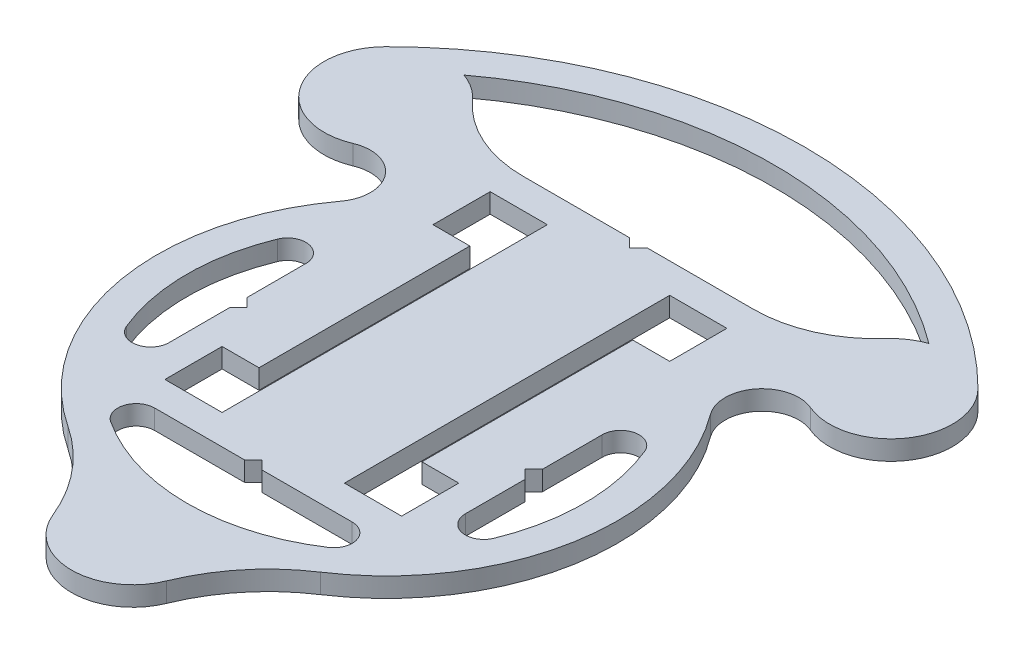
SolidWorks part; units mm, degrees
ref_plane "Front Plane" through (0, 0, 0) normal (0, 0, 1) x (1, 0, 0)
ref_plane "Top Plane" through (0, 0, 0) normal (0, 1, 0) x (1, 0, 0)
ref_plane "Right Plane" through (0, 0, 0) normal (1, 0, 0) x (0, 0, -1)
ref_plane "Plane1" through (0, 0, 26.3) normal (0, 0, 1) x (1, 0, 0)
ref_plane "Plane2" through (0, 0, 9.8) normal (0, 0, 1) x (1, 0, 0)
ref_axis "Axis1" through (0, 3.3337, 9.8) along (0, -1, 0)
sketch "Sketch1" plane through (0, 0, 0) normal (0, 1, 0) x (1, 0, 0)
  line L1 (-19.1, -26.3) -> (19.1, -26.3) construction
  line L2 (-19.1, -26.3) -> (-19.1, 26.3) construction
  line L4 (19.1, -26.3) -> (19.1, 26.3) construction
  line L5 (-19.1, -26.3) -> (19.1, 26.3) construction
  line L6 (-19.1, 26.3) -> (19.1, -26.3) construction
  line L10 (0, -9.8) -> (41.1, 31.3) construction
  line L19 (-19.1, 26.3) -> (19.1, 26.3) construction
  line L21 (0, -9.8) -> (-41.1, 31.3) construction
  line L22 (-41.1, 31.3) -> (41.1, 31.3) construction
  line L24 (0, -9.8) -> (0, 31.3) construction
  line L28 (41.1, 31.3) -> (48.1711, 38.3711) construction
  line L30 (24.1, -31.3) -> (24.1, 31.3) construction
  line L31 (-24.1, 31.3) -> (24.1, 31.3) construction
  line L32 (-24.1, -31.3) -> (-24.1, 31.3) construction
  line L33 (-24.1, -31.3) -> (24.1, -31.3) construction
  line L34 (0, -9.8) -> (0, -50.9) construction
  line L35 (-18.7393, 31.3) -> (18.7393, 31.3)
  line L36 (-19.1, -26.3) -> (-24.1, -31.3) construction
  line L38 (-24.1, -31.3) -> (-27.6405, -34.8405) construction
  line L40 (19.1, -26.3) -> (24.1, -31.3) construction
  line L42 (24.1, -31.3) -> (27.6405, -34.8405) construction
  line L43 (-24.1, -20.9298) -> (-24.1208, 1.6824)
  line L44 (24.1, -20.9298) -> (24.1, 1.3298)
  line L45 (-33.6464, -26.3) -> (-33.6464, 37.9667) construction
  line L46 (-33.6464, -26.3) -> (-19.1, -26.3) construction
  line L47 (-24.1, -22.6935) -> (-24.1, 6.3801) construction
  line L48 (-16.0634, -31.3) -> (16.0634, -31.3)
  circle A0 centre (-41.1, 31.3) radius 10 construction
  circle A1 centre (41.1, 31.3) radius 10 construction
  arc A2 (-48.1711, 38.3711) -> (48.1711, 38.3711) centre (0, -9.8) cw
  arc A3 (-37.814, 40.7447) -> (37.814, 40.7447) centre (0, -9.8) cw
  circle A4 centre (0, -50.9) radius 10 construction
  arc A5 (24.1, -31.3) -> (-24.1, -31.3) centre (0, -9.8) cw construction
  arc A7 (-33.6464, 37.9667) -> (-18.7393, 31.3) centre (-18.7393, 51.3) ccw
  arc A8 (18.7393, 31.3) -> (33.6464, 37.9667) centre (18.7393, 51.3) ccw
  arc A13 (-37.814, 40.7447) -> (-33.6464, 37.9667) centre (-41.1, 31.3) cw
  arc A14 (37.814, 40.7447) -> (33.6464, 37.9667) centre (41.1, 31.3) ccw
  arc A15 (27.6405, -34.8405) -> (-27.6405, -34.8405) centre (0, -9.8) cw construction
  arc A16 (9.2621, -54.6701) -> (20.5326, -40.9358) centre (37.0484, -65.9803) cw
  arc A17 (-20.5326, -40.9358) -> (-9.2621, -54.6701) centre (-37.0484, -65.9803) cw
  arc A24 (9.2621, -54.6701) -> (-9.2621, -54.6701) centre (0, -50.9) cw
  arc A26 (-37.1966, 22.0933) -> (-30.0379, 12.9916) centre (-34.8546, 16.5693) cw
  arc A27 (-30.0379, 12.9916) -> (-20.5326, -40.9358) centre (0.2124, -9.4778) ccw
  arc A28 (37.1966, 22.0933) -> (30.0379, 12.9916) centre (34.8546, 16.5693) ccw
  arc A29 (30.0379, 12.9916) -> (20.5326, -40.9358) centre (-0.2124, -9.4778) cw
  arc A30 (-24.1, 11.7) -> (24.1, 11.7) centre (0, -9.8) ccw construction
  arc A31 (-29.8751, 2.4695) -> (-24.1208, 1.6824) centre (-27.1, 1.3298) cw
  arc A32 (-24.1, -20.9298) -> (-29.8751, -22.0695) centre (-27.1, -20.9298) cw
  arc A33 (-17.7083, -36.8088) -> (-16.0634, -31.3) centre (-16.0634, -34.3) cw
  arc A34 (17.7083, -36.8088) -> (16.0634, -31.3) centre (16.0634, -34.3) ccw
  arc A35 (24.1, 1.3298) -> (29.8751, 2.4695) centre (27.1, 1.3298) cw
  arc A36 (29.8751, -22.0695) -> (24.1, -20.9298) centre (27.1, -20.9298) cw
  arc A37 (29.8751, 2.4695) -> (29.8751, -22.0695) centre (0, -9.8) cw
  arc A38 (-29.8751, -22.0695) -> (-29.8751, 2.4695) centre (0, -9.8) cw
  arc A39 (-17.7083, -36.8088) -> (17.7083, -36.8088) centre (0, -9.8) ccw
  arc A40 (-37.1966, 22.0933) -> (-48.1711, 38.3711) centre (-41.1, 31.3) cw
  arc A41 (37.1966, 22.0933) -> (48.1711, 38.3711) centre (41.1, 31.3) ccw
  point P0 (0, 0)
  point P59 (-26.6935, 4.3021)
  dimension "D5" = 5
  dimension "D8" = 30
  dimension "D9" = 3
  dimension "D10" = 6
  dimension "D3" = 20
  dimension "D4" = 5
  dimension "D6" = 20
  dimension "D7" = 5
  dimension "D1" = 38.2
  dimension "D2" = 52.6
extrude "Boss-Extrude1" add sketch "Sketch1" along normal blind 3.175
sketch "Sketch2" plane through (0, 3.175, 0) normal (0, 1, 0) x (1, 0, 0)
  line L0 (-10.1, 0) -> (10.1, 0) construction
  line L5 (-10.1, 26.3) -> (-10.1, -26.3) construction
  line L6 (10.1, 26.3) -> (10.1, -26.3) construction
  line L7 (-13.1, 17.3) -> (-13.1, -17.3) construction
  line L8 (13.1, 17.3) -> (13.1, -17.3) construction
  line L9 (-13.1, 0) -> (-10.1, 0) construction
  line L10 (10.1, 0) -> (13.1, 0) construction
  line L11 (-10.1, 26.3) -> (-19.1, 26.3) construction
  line L12 (-19.1, 26.3) -> (-19.1, 17.3) construction
  line L13 (-19.1, 17.3) -> (-13.1, 17.3) construction
  line L14 (-10.1, -26.3) -> (-19.1, -26.3) construction
  line L15 (-19.1, -26.3) -> (-19.1, -17.3) construction
  line L16 (-19.1, -17.3) -> (-13.1, -17.3) construction
  line L17 (10.1, 26.3) -> (19.1, 26.3) construction
  line L18 (19.1, 26.3) -> (19.1, 17.3) construction
  line L19 (19.1, 17.3) -> (13.1, 17.3) construction
  line L20 (10.1, -26.3) -> (19.1, -26.3) construction
  line L21 (19.1, -26.3) -> (19.1, -17.3) construction
  line L22 (19.1, -17.3) -> (13.1, -17.3) construction
  line L23 (-19.25, -17.15) -> (-13.25, -17.15)
  line L24 (-13.25, 17.15) -> (-13.25, -17.15)
  line L25 (-19.25, 17.15) -> (-13.25, 17.15)
  line L26 (-19.25, 26.45) -> (-19.25, 17.15)
  line L27 (-9.95, 26.45) -> (-19.25, 26.45)
  line L28 (-9.95, 26.45) -> (-9.95, -26.45)
  line L29 (-9.95, -26.45) -> (-19.25, -26.45)
  line L30 (-19.25, -26.45) -> (-19.25, -17.15)
  line L31 (19.25, -17.15) -> (13.25, -17.15)
  line L32 (13.25, 17.15) -> (13.25, -17.15)
  line L33 (19.25, 17.15) -> (13.25, 17.15)
  line L34 (19.25, 26.45) -> (19.25, 17.15)
  line L35 (9.95, 26.45) -> (19.25, 26.45)
  line L36 (9.95, 26.45) -> (9.95, -26.45)
  line L37 (9.95, -26.45) -> (19.25, -26.45)
  line L38 (19.25, -26.45) -> (19.25, -17.15)
  point P3 (0, 0)
  point P9 (-10.1, 0)
  point P12 (10.1, 0)
  point P15 (-13.1, 0)
  point P18 (13.1, 0)
  dimension "D1" = 20.2
  dimension "D2" = 52.6
  dimension "D3" = 3
  dimension "D4" = 34.6
  dimension "D5" = 9
  dimension "D6" = 0.15
  dimension "D7" = 0.15
extrude "Cut-Extrude3" cut sketch "Sketch2" against normal up to next
sketch "Sketch8" plane through (0, 3.175, 0) normal (0, 1, 0) x (1, 0, 0)
  line L0 (0, -9.8) -> (0, -31.3) construction
  line L1 (16.0634, -31.3) -> (-16.0634, -31.3) construction
  line L2 (0, -9.8) -> (-24.1104, -9.6237) construction
  line L3 (-24.1, -20.9298) -> (-24.1208, 1.6824) construction
  line L4 (0, -9.8) -> (24.1, -9.8) construction
  line L5 (24.1, 1.3298) -> (24.1, -20.9298) construction
  line L6 (0, -9.8) -> (0, 31.3) construction
  line L7 (-18.7393, 31.3) -> (18.7393, 31.3) construction
  line L8 (-22.702, -9.634) -> (-24.1117, -8.2152)
  line L9 (-24.1117, -8.2152) -> (-24.1091, -11.0321)
  line L10 (-24.1091, -11.0321) -> (-22.702, -9.634)
  line L11 (22.6858, -9.8) -> (24.1, -11.2142)
  line L12 (24.1, -11.2142) -> (24.1, -8.3858)
  line L13 (24.1, -8.3858) -> (22.6858, -9.8)
  line L14 (0, -29.8858) -> (-1.4142, -31.3)
  line L15 (-1.4142, -31.3) -> (1.4142, -31.3)
  line L16 (1.4142, -31.3) -> (0, -29.8858)
  line L17 (0, 29.8858) -> (-1.4142, 31.3)
  line L18 (-1.4142, 31.3) -> (1.4142, 31.3)
  line L19 (1.4142, 31.3) -> (0, 29.8858)
  point P16 (-24.1104, -9.6237)
  point P20 (24.1, -9.8)
  point P24 (0, -31.3)
  point P28 (0, 31.3)
  dimension "D1" = 2
extrude "Cut-Extrude4" cut sketch "Sketch8" against normal up to next
sketch "Sketch9" plane through (0, 3.175, 0) normal (0, 1, 0) x (1, 0, 0)
  line L1 (-48.1711, 38.3711) -> (-44.6355, 34.8355)
  line L2 (-34.0621, 49.1973) -> (-31.5621, 44.8671)
  line L3 (-17.6318, 56.0029) -> (-16.3377, 51.1733)
  line L4 (0, 58.3242) -> (0, 53.3242)
  line L5 (17.6318, 56.0029) -> (16.3377, 51.1733)
  line L6 (34.0621, 49.1973) -> (31.5621, 44.8671)
  line L7 (48.1711, 38.3711) -> (44.6355, 34.8355)
  line L8 (-48.1711, 38.3711) -> (-46.4033, 36.6033)
  line L9 (-43.7894, 42.3861) -> (-42.1824, 40.471)
  line L10 (-39.0744, 46.0041) -> (-37.6405, 43.9562)
  line L11 (-34.0621, 49.1973) -> (-32.8121, 47.0322)
  line L12 (-28.7905, 51.9415) -> (-27.734, 49.6757)
  line L13 (-23.2998, 54.2158) -> (-22.4448, 51.8666)
  line L14 (-17.6318, 56.0029) -> (-16.9848, 53.5881)
  line L15 (-11.8296, 57.2892) -> (-11.3955, 54.8272)
  line L16 (-5.9374, 58.0649) -> (-5.7195, 55.5745)
  line L17 (0, 58.3242) -> (0, 55.8242)
  line L18 (5.9374, 58.0649) -> (5.7195, 55.5745)
  line L19 (11.8296, 57.2892) -> (11.3955, 54.8272)
  line L20 (17.6318, 56.0029) -> (16.9848, 53.5881)
  line L21 (23.2998, 54.2158) -> (22.4448, 51.8666)
  line L22 (28.7905, 51.9415) -> (27.734, 49.6757)
  line L23 (34.0621, 49.1973) -> (32.8121, 47.0322)
  line L24 (39.0744, 46.0041) -> (37.6405, 43.9562)
  line L25 (43.7894, 42.3861) -> (42.1824, 40.471)
  line L26 (48.1711, 38.3711) -> (46.4033, 36.6033)
  line L27 (-48.1711, 38.3711) -> (-47.2872, 37.4872)
  line L28 (-47.323, 39.2044) -> (-46.4547, 38.3053)
  line L29 (-46.4606, 40.0229) -> (-45.6081, 39.1087)
  line L30 (-45.584, 40.8261) -> (-44.7476, 39.8972)
  line L31 (-44.6935, 41.614) -> (-43.8734, 40.6706)
  line L32 (-43.7894, 42.3861) -> (-42.9859, 41.4286)
  line L33 (-42.8719, 43.1424) -> (-42.0853, 42.171)
  line L34 (-41.9414, 43.8826) -> (-41.1719, 42.8976)
  line L35 (-40.9982, 44.6064) -> (-40.2459, 43.6081)
  line L36 (-40.0424, 45.3136) -> (-39.3077, 44.3023)
  line L37 (-39.0744, 46.0041) -> (-38.3575, 44.9801)
  line L38 (-38.0946, 46.6775) -> (-37.3956, 45.6412)
  line L39 (-37.1031, 47.3337) -> (-36.4223, 46.2854)
  line L40 (-36.1003, 47.9726) -> (-35.4379, 46.9125)
  line L41 (-35.0865, 48.5938) -> (-34.4427, 47.5224)
  line L42 (-34.0621, 49.1973) -> (-33.4371, 48.1147)
  line L43 (-33.0273, 49.7827) -> (-32.4212, 48.6895)
  line L44 (-31.9824, 50.3501) -> (-31.3955, 49.2464)
  line L45 (-30.9277, 50.8991) -> (-30.3602, 49.7853)
  line L46 (-29.8637, 51.4296) -> (-29.3157, 50.3061)
  line L47 (-28.7905, 51.9415) -> (-28.2622, 50.8086)
  line L48 (-27.7086, 52.4345) -> (-27.2002, 51.2926)
  line L49 (-26.6182, 52.9086) -> (-26.1298, 51.758)
  line L50 (-25.5198, 53.3636) -> (-25.0515, 52.2047)
  line L51 (-24.4135, 53.7994) -> (-23.9656, 52.6324)
  line L52 (-23.2998, 54.2158) -> (-22.8723, 53.0412)
  line L53 (-22.1791, 54.6127) -> (-21.7721, 53.4308)
  line L54 (-21.0515, 54.9899) -> (-20.6653, 53.8011)
  line L55 (-19.9176, 55.3475) -> (-19.5521, 54.1521)
  line L56 (-18.7776, 55.6852) -> (-18.433, 54.4836)
  line L57 (-17.6318, 56.0029) -> (-17.3083, 54.7955)
  line L58 (-16.4807, 56.3006) -> (-16.1783, 55.0877)
  line L59 (-15.3246, 56.5782) -> (-15.0434, 55.3602)
  line L60 (-14.1638, 56.8355) -> (-13.9039, 55.6128)
  line L61 (-12.9987, 57.0725) -> (-12.7602, 55.8455)
  line L62 (-11.8296, 57.2892) -> (-11.6126, 56.0582)
  line L63 (-10.657, 57.4855) -> (-10.4614, 56.2508)
  line L64 (-9.4811, 57.6612) -> (-9.3071, 56.4234)
  line L65 (-8.3022, 57.8164) -> (-8.1499, 56.5757)
  line L66 (-7.1209, 57.951) -> (-6.9903, 56.7078)
  line L67 (-5.9374, 58.0649) -> (-5.8285, 56.8197)
  line L68 (-4.7521, 58.1582) -> (-4.6649, 56.9113)
  line L69 (-3.5653, 58.2308) -> (-3.4999, 56.9825)
  line L70 (-2.3775, 58.2827) -> (-2.3339, 57.0334)
  line L71 (-1.1889, 58.3138) -> (-1.1671, 57.064)
  line L72 (0, 58.3242) -> (0, 57.0742)
  line L73 (1.1889, 58.3138) -> (1.1671, 57.064)
  line L74 (2.3775, 58.2827) -> (2.3339, 57.0334)
  line L75 (3.5653, 58.2308) -> (3.4999, 56.9825)
  line L76 (4.7521, 58.1582) -> (4.6649, 56.9113)
  line L77 (5.9374, 58.0649) -> (5.8285, 56.8197)
  line L78 (7.1209, 57.951) -> (6.9903, 56.7078)
  line L79 (8.3022, 57.8164) -> (8.1499, 56.5757)
  line L80 (9.4811, 57.6612) -> (9.3071, 56.4234)
  line L81 (10.657, 57.4855) -> (10.4614, 56.2508)
  line L82 (11.8296, 57.2892) -> (11.6126, 56.0582)
  line L83 (12.9987, 57.0725) -> (12.7602, 55.8455)
  line L84 (14.1638, 56.8355) -> (13.9039, 55.6128)
  line L85 (15.3246, 56.5782) -> (15.0434, 55.3602)
  line L86 (16.4807, 56.3006) -> (16.1783, 55.0877)
  line L87 (17.6318, 56.0029) -> (17.3083, 54.7955)
  line L88 (18.7776, 55.6852) -> (18.433, 54.4836)
  line L89 (19.9176, 55.3475) -> (19.5521, 54.1521)
  line L90 (21.0515, 54.9899) -> (20.6653, 53.8011)
  line L91 (22.1791, 54.6127) -> (21.7721, 53.4308)
  line L92 (23.2998, 54.2158) -> (22.8723, 53.0412)
  line L93 (24.4135, 53.7994) -> (23.9656, 52.6324)
  line L94 (25.5198, 53.3636) -> (25.0515, 52.2047)
  line L95 (26.6182, 52.9086) -> (26.1298, 51.758)
  line L96 (27.7086, 52.4345) -> (27.2002, 51.2926)
  line L97 (28.7905, 51.9415) -> (28.2622, 50.8086)
  line L98 (29.8637, 51.4296) -> (29.3157, 50.3061)
  line L99 (30.9277, 50.8991) -> (30.3602, 49.7853)
  line L100 (31.9824, 50.3501) -> (31.3955, 49.2464)
  line L101 (33.0273, 49.7827) -> (32.4212, 48.6895)
  line L102 (34.0621, 49.1973) -> (33.4371, 48.1147)
  line L103 (35.0865, 48.5938) -> (34.4427, 47.5224)
  line L104 (36.1003, 47.9726) -> (35.4379, 46.9125)
  line L105 (37.1031, 47.3337) -> (36.4223, 46.2854)
  line L106 (38.0946, 46.6775) -> (37.3956, 45.6412)
  line L107 (39.0744, 46.0041) -> (38.3575, 44.9801)
  line L108 (40.0424, 45.3136) -> (39.3077, 44.3023)
  line L109 (40.9982, 44.6064) -> (40.2459, 43.6081)
  line L110 (41.9414, 43.8826) -> (41.1719, 42.8976)
  line L111 (42.8719, 43.1424) -> (42.0853, 42.171)
  line L112 (43.7894, 42.3861) -> (42.9859, 41.4286)
  line L113 (44.6935, 41.614) -> (43.8734, 40.6706)
  line L114 (45.584, 40.8261) -> (44.7476, 39.8972)
  line L115 (46.4606, 40.0229) -> (45.6081, 39.1087)
  line L116 (47.323, 39.2044) -> (46.4547, 38.3053)
  line L117 (48.1711, 38.3711) -> (47.2872, 37.4872)
  dimension "D1" = 5
  dimension "D3" = 2.5
  dimension "D5" = 1.25
  dimension "D2" = 7
  dimension "D4" = 19
  dimension "D6" = 91
equation "\"D7@Sketch2\"=\"D6@Sketch2\""
